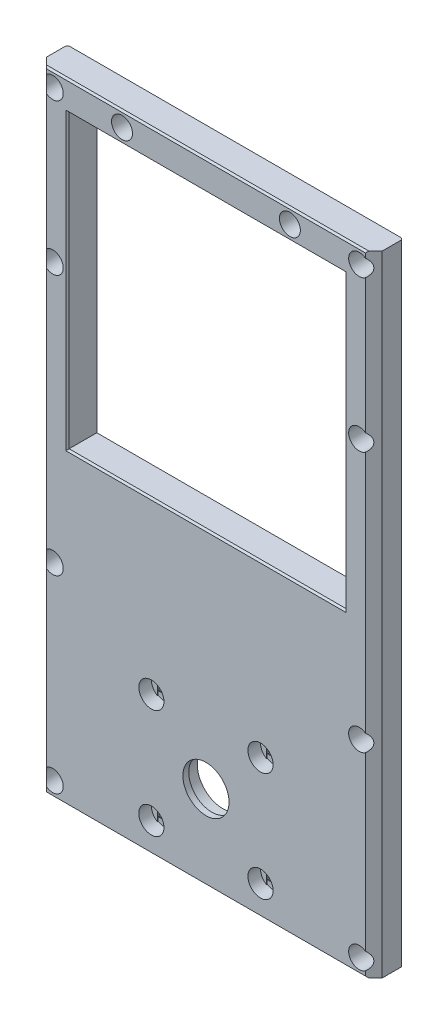
SolidWorks part; units mm, degrees
ref_plane "Front Plane" through (0, 0, 0) normal (0, 0, 1) x (1, 0, 0)
ref_plane "Top Plane" through (0, 0, 0) normal (0, 1, 0) x (1, 0, 0)
ref_plane "Right Plane" through (0, 0, 0) normal (1, 0, 0) x (0, 0, -1)
sketch "Sketch1" plane through (0, 0, 0) normal (0, 0, 1) x (1, 0, 0)
  line L1 (-40, -75) -> (40, -75)
  line L2 (-40, -75) -> (-40, 75)
  line L3 (-40, 75) -> (40, 75)
  line L4 (40, -75) -> (40, 75)
  line L5 (-40, -75) -> (40, 75) construction
  line L6 (-40, 75) -> (40, -75) construction
  line L7 (-33, -68) -> (33, -68)
  line L8 (-33, -68) -> (-33, 68)
  line L9 (-33, 68) -> (33, 68)
  line L10 (33, -68) -> (33, 68)
  line L11 (-33, -68) -> (33, 68) construction
  line L12 (-33, 68) -> (33, -68) construction
  point P0 (0, 0)
  point P6 (0, 0)
  dimension "D1" = 150
  dimension "D2" = 80
  dimension "D3" = 7
  dimension "D4" = 7
extrude "Boss-Extrude1" add sketch "Sketch1" along normal blind 7
sketch "Sketch2" plane through (0, 0, 7) normal (0, 0, 1) x (1, 0, 0)
  line L0 (33, -68) -> (33, 68) construction
  line L1 (-33, -68) -> (33, -68)
  line L2 (-33, -68) -> (-33, -32)
  line L3 (-33, -32) -> (33, -32)
  line L4 (33, -68) -> (33, -32)
  dimension "D1" = 36
extrude "Boss-Extrude2" add sketch "Sketch2" against normal up to surface (7 mm away) up to face at (0, 0, 0)
sketch "Sketch3" plane through (0, 0, 0) normal (0, 0, -1) x (-1, 0, 0)
  line L0 (0, -75) -> (0, -55) construction
  line L1 (40, -75) -> (-40, -75) construction
  circle A0 centre (0, -55) radius 5.5
  dimension "D1" = 11
  dimension "D2" = 20
extrude "Cut-Extrude1" cut sketch "Sketch3" against normal through all
sketch "Sketch4" plane through (0, 0, 0) normal (0, 0, -1) x (-1, 0, 0)
  circle A0 centre (0, -55) radius 6.05
  dimension "D1" = 12.1
extrude "Cut-Extrude2" cut sketch "Sketch4" against normal offset from surface (5.6 mm away) 1.4 up to face at (-5.5, -55, 7)
sketch "Sketch5" plane through (0, 0, 0) normal (0, 0, -1) x (-1, 0, 0)
  circle A0 centre (0, -55) radius 11
  dimension "D1" = 22
extrude "Cut-Extrude3" cut sketch "Sketch5" against normal offset from surface (3 mm away) 2.6 up to face at (-6.05, -55, 5.6)
sketch "Sketch6" plane through (0, 0, 0) normal (0, 0, -1) x (-1, 0, 0)
  line L1 (-13, -68) -> (13, -68) construction
  line L2 (-13, -68) -> (-13, -42) construction
  line L3 (-13, -42) -> (13, -42) construction
  line L4 (13, -68) -> (13, -42) construction
  line L5 (-13, -68) -> (13, -42) construction
  line L6 (-13, -42) -> (13, -68) construction
  circle A0 centre (-13, -42) radius 1.6
  circle A1 centre (13, -42) radius 1.6
  circle A2 centre (13, -68) radius 1.6
  circle A3 centre (-13, -68) radius 1.6
  point P0 (0, -55)
  dimension "D2" = 3.2
  dimension "D1" = 26
extrude "Cut-Extrude4" cut sketch "Sketch6" against normal through all
sketch "Sketch7" plane through (0, 0, 0) normal (0, 0, -1) x (-1, 0, 0)
  line L1 (-25, -74) -> (25, -74)
  line L2 (-25, -74) -> (-25, -36)
  line L3 (-25, -36) -> (25, -36)
  line L4 (25, -74) -> (25, -36)
  line L5 (-25, -74) -> (25, -36) construction
  line L6 (-25, -36) -> (25, -74) construction
  point P0 (0, -55)
  dimension "D1" = 50
  dimension "D2" = 38
extrude "Cut-Extrude5" cut sketch "Sketch7" against normal blind 1
sketch "Sketch8" plane through (0, 0, 7) normal (0, 0, 1) x (1, 0, 0)
  circle A0 centre (-13, -42) radius 3
  circle A1 centre (13, -42) radius 3
  circle A2 centre (13, -68) radius 3
  circle A3 centre (-13, -68) radius 3
  dimension "D1" = 6
extrude "Cut-Extrude6" cut sketch "Sketch8" against normal blind 3
sketch "Sketch9" plane through (0, 0, 7) normal (0, 0, 1) x (1, 0, 0)
  line L0 (-40, 75) -> (-40, -75) construction
  line L1 (-36.5, -71.5) -> (36.5, -71.5) construction
  line L2 (-36.5, -71.5) -> (-36.5, 71.5) construction
  line L3 (-36.5, 71.5) -> (36.5, 71.5) construction
  line L4 (36.5, -71.5) -> (36.5, 71.5) construction
  line L5 (-36.5, -71.5) -> (36.5, 71.5) construction
  line L6 (-36.5, 71.5) -> (36.5, -71.5) construction
  line L7 (40, 75) -> (-40, 75) construction
  circle A0 centre (-36.5, 71.5) radius 1.35
  circle A1 centre (36.5, 71.5) radius 1.35
  circle A2 centre (36.5, -71.5) radius 1.35
  circle A3 centre (-36.5, -71.5) radius 1.35
  circle A6 centre (-36.5, 35.5) radius 1.35
  circle A7 centre (-36.5, -26.5) radius 1.35
  circle A8 centre (36.5, -26.5) radius 1.35
  circle A9 centre (36.5, 35.5) radius 1.35
  point P0 (0, 0)
  dimension "D3" = 2.7
  dimension "D4" = 45
  dimension "D5" = 36
  dimension "D1" = 3.5
  dimension "D2" = 3.5
extrude "Cut-Extrude7" cut sketch "Sketch9" against normal through all
sketch "Sketch10" plane through (0, 0, 7) normal (0, 0, 1) x (1, 0, 0)
  circle A0 centre (-36.5, 71.5) radius 2.5
  circle A1 centre (36.5, 71.5) radius 2.5
  circle A2 centre (-36.5, 35.5) radius 2.5
  circle A3 centre (-36.5, -26.5) radius 2.5
  circle A4 centre (-36.5, -71.5) radius 2.5
  circle A5 centre (36.5, -71.5) radius 2.5
  circle A6 centre (36.5, 35.5) radius 2.5
  circle A7 centre (36.5, -26.5) radius 2.5
  dimension "D1" = 5
extrude "Cut-Extrude8" cut sketch "Sketch10" against normal blind 5
chamfer "Chamfer1" distance 2 angle 45 2 edges at (-40, 0, 7) (40, 0, 7)
sketch "Sketch11" plane through (0, 0, 7) normal (0, 0, 1) x (1, 0, 0)
  line L0 (33, -32) -> (33, 68) construction
  line L1 (-33, -32) -> (33, -32)
  line L2 (-33, -32) -> (-33, -1.5)
  line L3 (-33, -1.5) -> (33, -1.5)
  line L4 (33, -32) -> (33, -1.5)
  line L5 (-38, -75) -> (38, -75) construction
  dimension "D1" = 73.5
extrude "Boss-Extrude3" add sketch "Sketch11" against normal up to surface (7 mm away) up to face at (37.85, 71.5, 0)
sketch "Sketch12" plane through (0, 0, 2) normal (0, 0, 1) x (1, 0, 0)
  line L2 (-37.85, -73.6042) -> (-37.85, -69.3958)
  line L4 (-35.15, -73.6042) -> (-35.15, -69.3958)
  line L5 (-37.85, -73.6042) -> (-35.15, -69.3958) construction
  line L6 (-37.85, -69.3958) -> (-35.15, -73.6042) construction
  line L8 (-37.85, -28.6042) -> (-37.85, -24.3958)
  line L10 (-35.15, -28.6042) -> (-35.15, -24.3958)
  line L11 (-37.85, -28.6042) -> (-35.15, -24.3958) construction
  line L12 (-37.85, -24.3958) -> (-35.15, -28.6042) construction
  line L14 (-37.85, 33.3958) -> (-37.85, 37.6042)
  line L16 (-35.15, 33.3958) -> (-35.15, 37.6042)
  line L17 (-37.85, 33.3958) -> (-35.15, 37.6042) construction
  line L18 (-37.85, 37.6042) -> (-35.15, 33.3958) construction
  line L20 (-37.85, 69.3958) -> (-37.85, 73.6042)
  line L22 (-35.15, 69.3958) -> (-35.15, 73.6042)
  line L23 (-37.85, 69.3958) -> (-35.15, 73.6042) construction
  line L24 (-37.85, 73.6042) -> (-35.15, 69.3958) construction
  arc A0 (-38, -73.5) -> (-38, -69.5) centre (-36.5, -71.5) ccw construction
  circle A1 centre (-36.5, -26.5) radius 2.5 construction
  circle A2 centre (-36.5, 35.5) radius 2.5 construction
  arc A3 (-38, 69.5) -> (-38, 73.5) centre (-36.5, 71.5) ccw construction
  circle A4 centre (-36.5, 71.5) radius 1.35 construction
  circle A5 centre (-36.5, 71.5) radius 2.5 construction
  arc A6 (-35.15, 73.6042) -> (-37.85, 73.6042) centre (-36.5, 71.5) ccw
  arc A7 (-37.85, 69.3958) -> (-35.15, 69.3958) centre (-36.5, 71.5) ccw
  circle A8 centre (-36.5, 35.5) radius 1.35 construction
  arc A9 (-37.85, 33.3958) -> (-35.15, 33.3958) centre (-36.5, 35.5) ccw
  arc A10 (-35.15, 37.6042) -> (-37.85, 37.6042) centre (-36.5, 35.5) ccw
  circle A11 centre (-36.5, -26.5) radius 1.35 construction
  arc A12 (-37.85, -28.6042) -> (-35.15, -28.6042) centre (-36.5, -26.5) ccw
  arc A13 (-35.15, -24.3958) -> (-37.85, -24.3958) centre (-36.5, -26.5) ccw
  circle A14 centre (-36.5, -71.5) radius 1.35 construction
  arc A16 (-37.85, -73.6042) -> (-35.15, -73.6042) centre (-36.5, -71.5) ccw
  arc A18 (-35.15, -69.3958) -> (-37.85, -69.3958) centre (-36.5, -71.5) ccw
  point P0 (-36.5, -71.5)
  point P9 (-36.5, -26.5)
  point P17 (-36.5, 35.5)
  point P25 (-36.5, 71.5)
extrude "Cut-Extrude9" cut sketch "Sketch12" against normal blind 0.2
sketch "Sketch13" plane through (0, 0, 1.8) normal (0, 0, 1) x (1, 0, 0)
  line L0 (-35.15, -71.5) -> (-35.15, -69.3958) construction
  line L1 (-37.85, -72.85) -> (-35.15, -72.85)
  line L2 (-37.85, -72.85) -> (-37.85, -70.15)
  line L3 (-37.85, -70.15) -> (-35.15, -70.15)
  line L4 (-35.15, -72.85) -> (-35.15, -70.15)
  line L5 (-37.85, -72.85) -> (-35.15, -70.15) construction
  line L6 (-37.85, -70.15) -> (-35.15, -72.85) construction
  line L7 (-35.15, -26.5) -> (-35.15, -24.3958) construction
  line L8 (-37.85, -27.85) -> (-35.15, -27.85)
  line L9 (-37.85, -27.85) -> (-37.85, -25.15)
  line L10 (-37.85, -25.15) -> (-35.15, -25.15)
  line L11 (-35.15, -27.85) -> (-35.15, -25.15)
  line L12 (-37.85, -27.85) -> (-35.15, -25.15) construction
  line L13 (-37.85, -25.15) -> (-35.15, -27.85) construction
  line L14 (-35.15, 33.3958) -> (-35.15, 37.6042) construction
  line L15 (-37.85, 34.15) -> (-35.15, 34.15)
  line L16 (-37.85, 34.15) -> (-37.85, 36.85)
  line L17 (-37.85, 36.85) -> (-35.15, 36.85)
  line L18 (-35.15, 34.15) -> (-35.15, 36.85)
  line L19 (-37.85, 34.15) -> (-35.15, 36.85) construction
  line L20 (-37.85, 36.85) -> (-35.15, 34.15) construction
  line L21 (-35.15, 69.3958) -> (-35.15, 73.6042) construction
  line L22 (-37.85, 70.15) -> (-35.15, 70.15)
  line L23 (-37.85, 70.15) -> (-37.85, 72.85)
  line L24 (-37.85, 72.85) -> (-35.15, 72.85)
  line L25 (-35.15, 70.15) -> (-35.15, 72.85)
  line L26 (-37.85, 70.15) -> (-35.15, 72.85) construction
  line L27 (-37.85, 72.85) -> (-35.15, 70.15) construction
  arc A0 (-35.15, -71.5) -> (-37.85, -71.5) centre (-36.5, -71.5) ccw construction
  arc A1 (-35.15, -26.5) -> (-37.85, -26.5) centre (-36.5, -26.5) ccw construction
  arc A2 (-35.15, 35.5) -> (-37.85, 35.5) centre (-36.5, 35.5) ccw construction
  arc A3 (-35.15, 71.5) -> (-37.85, 71.5) centre (-36.5, 71.5) ccw construction
  point P0 (-36.5, -71.5)
  point P11 (-36.5, -26.5)
  point P22 (-36.5, 35.5)
  point P33 (-36.5, 71.5)
extrude "Cut-Extrude10" cut sketch "Sketch13" against normal blind 0.2
sketch "Sketch14" plane through (0, 0, 4) normal (0, 0, 1) x (1, 0, 0)
  line L2 (-14.6, -44.5377) -> (-14.6, -39.4623)
  line L4 (-11.4, -44.5377) -> (-11.4, -39.4623)
  line L5 (-14.6, -44.5377) -> (-11.4, -39.4623) construction
  line L6 (-14.6, -39.4623) -> (-11.4, -44.5377) construction
  line L8 (-14.6, -70.5377) -> (-14.6, -65.4623)
  line L10 (-11.4, -70.5377) -> (-11.4, -65.4623)
  line L11 (-14.6, -70.5377) -> (-11.4, -65.4623) construction
  line L12 (-14.6, -65.4623) -> (-11.4, -70.5377) construction
  circle A0 centre (-13, -42) radius 3 construction
  circle A1 centre (-13, -68) radius 3 construction
  circle A2 centre (-13, -42) radius 3 construction
  arc A3 (-14.6, -44.5377) -> (-11.4, -44.5377) centre (-13, -42) ccw
  arc A4 (-14.6, -70.5377) -> (-11.4, -70.5377) centre (-13, -68) ccw
  circle A5 centre (-13, -42) radius 1.6 construction
  circle A6 centre (-13, -68) radius 1.6 construction
  arc A7 (-11.4, -39.4623) -> (-14.6, -39.4623) centre (-13, -42) ccw
  arc A8 (-11.4, -65.4623) -> (-14.6, -65.4623) centre (-13, -68) ccw
  point P0 (-13, -42)
  point P8 (-13, -68)
extrude "Cut-Extrude11" cut sketch "Sketch14" against normal blind 0.2
sketch "Sketch15" plane through (0, 0, 3.8) normal (0, 0, 1) x (1, 0, 0)
  line L0 (-11.4, -42) -> (-11.4, -39.4623) construction
  line L1 (-14.6, -43.6) -> (-11.4, -43.6)
  line L2 (-14.6, -43.6) -> (-14.6, -40.4)
  line L3 (-14.6, -40.4) -> (-11.4, -40.4)
  line L4 (-11.4, -43.6) -> (-11.4, -40.4)
  line L5 (-14.6, -43.6) -> (-11.4, -40.4) construction
  line L6 (-14.6, -40.4) -> (-11.4, -43.6) construction
  line L7 (-11.4, -68) -> (-11.4, -65.4623) construction
  line L8 (-14.6, -69.6) -> (-11.4, -69.6)
  line L9 (-14.6, -69.6) -> (-14.6, -66.4)
  line L10 (-14.6, -66.4) -> (-11.4, -66.4)
  line L11 (-11.4, -69.6) -> (-11.4, -66.4)
  line L12 (-14.6, -69.6) -> (-11.4, -66.4) construction
  line L13 (-14.6, -66.4) -> (-11.4, -69.6) construction
  arc A0 (-11.4, -68) -> (-14.6, -68) centre (-13, -68) ccw construction
  arc A1 (-14.6, -42) -> (-11.4, -42) centre (-13, -42) ccw construction
  point P0 (-13, -42)
  point P8 (-13, -68)
extrude "Cut-Extrude12" cut sketch "Sketch15" against normal blind 0.2
mirror "Mirror1" about plane through (0, 0, 0) normal (1, 0, 0) of "Cut-Extrude10", "Cut-Extrude11", "Cut-Extrude12", "Cut-Extrude9"
chamfer "Chamfer2" distance 0.4 angle 45 4 edges at (33, 33.25, 7) (0, 68, 7) (0, -1.5, 7) (-33, 33.25, 7)
chamfer "Chamfer3" distance 0.4 angle 45 4 edges at (-40, 0, 0) (40, 0, 0) (0, -75, 7) (0, 75, 7)
sketch "Sketch16" plane through (0, 0, 0) normal (1, 0, 0) x (0, 0, -1)
  line L0 (0, -4) -> (0, -15.4)
  line L1 (0, 75) -> (0, -75) construction
  line L2 (0, -15.4) -> (3.2, -12.2)
  line L3 (3.2, -12.2) -> (3.2, -7.2)
  line L4 (3.2, -7.2) -> (0, -4)
  line L5 (0, -15.4) -> (0, -19.4) construction
  line L6 (0.6, -7.7) -> (2.6, -7.7)
  line L7 (0.6, -7.7) -> (0.6, -11.7)
  line L8 (0.6, -11.7) -> (2.6, -11.7)
  line L9 (2.6, -7.7) -> (2.6, -11.7)
  line L10 (0, -17.4) -> (13.8851, -17.4) construction
  line L11 (2.6, -27.1) -> (2.6, -23.1)
  line L12 (0.6, -23.1) -> (2.6, -23.1)
  line L13 (0.6, -27.1) -> (0.6, -23.1)
  line L14 (0.6, -27.1) -> (2.6, -27.1)
  line L15 (3.2, -27.6) -> (0, -30.8)
  line L16 (3.2, -22.6) -> (3.2, -27.6)
  line L17 (0, -19.4) -> (3.2, -22.6)
  line L18 (0, -30.8) -> (0, -19.4)
  point P10 (2.6, -9.7)
  point P11 (3.2, -9.7)
  point P24 (0, -17.4)
  dimension "D1" = 5
  dimension "D2" = 2
  dimension "D3" = 0.6
  dimension "D4" = 0.6
  dimension "D5" = 45
  dimension "D6" = 4
  dimension "D7" = 4
  dimension "D8" = 4
extrude "Boss-Extrude4" add sketch "Sketch16" along normal mid plane 2
pattern_linear "LPattern1" count 2 spacing 20 along (1, 0, 0) count 2 spacing 20 along (-1, 0, 0) of "Boss-Extrude4"
sketch "Sketch17" plane through (0, 0, 0) normal (0, 0, -1) x (-1, 0, 0)
  line L0 (-20, 71.5) -> (20, 71.5) construction
  line L1 (-39.6, 75) -> (39.6, 75) construction
  circle A0 centre (-36.5, 71.5) radius 1.35 construction
  circle A1 centre (-36.5, 71.5) radius 1.35 construction
  circle A2 centre (-20, 71.5) radius 1.35
  circle A3 centre (20, 71.5) radius 1.35
  point P3 (0, 71.5)
  point P6 (0, 75)
  dimension "D1" = 40
extrude "Cut-Extrude13" cut sketch "Sketch17" against normal through all
sketch "Sketch18" plane through (0, 0, 7) normal (0, 0, 1) x (1, 0, 0)
  circle A0 centre (-20, 71.5) radius 2.5
  circle A1 centre (20, 71.5) radius 2.5
  arc A2 (-38, 69.5) -> (-38, 73.5) centre (-36.5, 71.5) ccw construction
extrude "Cut-Extrude14" cut sketch "Sketch18" against normal up to surface (5 mm away) up to face at (38.425, 71.5, 2)
sketch "Sketch19" plane through (0, 0, 2) normal (0, 0, 1) x (1, 0, 0)
  line L2 (-21.35, 69.3958) -> (-21.35, 73.6042)
  line L4 (-18.65, 69.3958) -> (-18.65, 73.6042)
  line L5 (-21.35, 69.3958) -> (-18.65, 73.6042) construction
  line L6 (-21.35, 73.6042) -> (-18.65, 69.3958) construction
  line L8 (18.65, 69.3958) -> (18.65, 73.6042)
  line L10 (21.35, 69.3958) -> (21.35, 73.6042)
  line L11 (18.65, 69.3958) -> (21.35, 73.6042) construction
  line L12 (18.65, 73.6042) -> (21.35, 69.3958) construction
  circle A0 centre (-20, 71.5) radius 2.5 construction
  circle A1 centre (20, 71.5) radius 2.5 construction
  circle A2 centre (20, 71.5) radius 1.35 construction
  circle A3 centre (-20, 71.5) radius 1.35 construction
  circle A4 centre (-20, 71.5) radius 2.5 construction
  arc A5 (18.65, 69.3958) -> (21.35, 69.3958) centre (20, 71.5) ccw
  arc A6 (-18.65, 73.6042) -> (-21.35, 73.6042) centre (-20, 71.5) ccw
  arc A7 (21.35, 73.6042) -> (18.65, 73.6042) centre (20, 71.5) ccw
  arc A8 (-21.35, 69.3958) -> (-18.65, 69.3958) centre (-20, 71.5) ccw
  point P0 (-20, 71.5)
  point P8 (20, 71.5)
extrude "Cut-Extrude15" cut sketch "Sketch19" against normal blind 0.2
sketch "Sketch20" plane through (0, 0, 1.8) normal (0, 0, 1) x (1, 0, 0)
  line L0 (-18.65, 69.3958) -> (-18.65, 73.6042) construction
  line L1 (-21.35, 70.15) -> (-18.65, 70.15)
  line L2 (-21.35, 70.15) -> (-21.35, 72.85)
  line L3 (-21.35, 72.85) -> (-18.65, 72.85)
  line L4 (-18.65, 70.15) -> (-18.65, 72.85)
  line L5 (-21.35, 70.15) -> (-18.65, 72.85) construction
  line L6 (-21.35, 72.85) -> (-18.65, 70.15) construction
  line L7 (21.35, 71.5) -> (21.35, 73.6042) construction
  line L8 (18.65, 70.15) -> (21.35, 70.15)
  line L9 (18.65, 70.15) -> (18.65, 72.85)
  line L10 (18.65, 72.85) -> (21.35, 72.85)
  line L11 (21.35, 70.15) -> (21.35, 72.85)
  line L12 (18.65, 70.15) -> (21.35, 72.85) construction
  line L13 (18.65, 72.85) -> (21.35, 70.15) construction
  arc A0 (18.65, 71.5) -> (21.35, 71.5) centre (20, 71.5) ccw construction
  point P0 (-20, 71.5)
  point P8 (20, 71.5)
extrude "Cut-Extrude16" cut sketch "Sketch20" against normal blind 0.2
